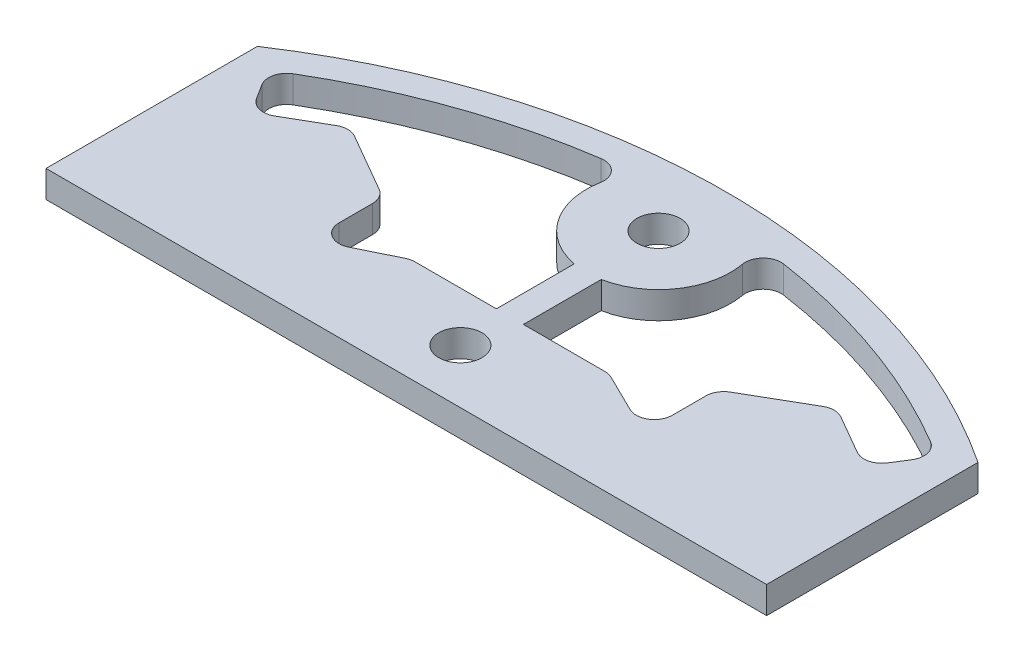
SolidWorks part; units mm, degrees
material "Acrylic (Medium-high impact)"
ref_plane "Front Plane" through (0, 0, 0) normal (0, 0, 1) x (1, 0, 0)
ref_plane "Top Plane" through (0, 0, 0) normal (0, 1, 0) x (1, 0, 0)
ref_plane "Right Plane" through (0, 0, 0) normal (1, 0, 0) x (0, 0, -1)
sketch "Sketch1" plane through (0, 0, 0) normal (0, 1, 0) x (1, 0, 0)
  line L0 (0, -85) -> (-32.4891, -64.8129) construction
  line L1 (0, -85) -> (0, 0) construction
  arc A0 (36.5434, -62.6165) -> (-36.5434, -62.6165) centre (0, 0) ccw
  arc A1 (30.0898, -61.3851) -> (-30.0898, -61.3851) centre (0, -85) ccw
  arc A2 (-30.0898, -61.3851) -> (-36.5434, -62.6165) centre (-34.0231, -58.2982) cw
  arc A3 (36.5434, -62.6165) -> (30.0898, -61.3851) centre (34.0231, -58.2982) cw
  dimension "D1" = 145
  dimension "D2" = 76.5
  dimension "D4" = 5
  dimension "D3" = 85
extrude "Boss-Extrude1" add sketch "Sketch1" along normal blind 3
sketch "Sketch10" plane through (0, 0, 0) normal (0, -1, 0) x (1, 0, 0)
  line L21 (-18.5, -44.8246) -> (-18.5, -52.9075)
  line L22 (-18.5, -52.9075) -> (-27, -57.815)
  line L23 (-27, -57.815) -> (-34, -53.7735)
  line L24 (-18.5, -48.0319) -> (-18.5, -51.7528)
  line L25 (-19.5, -53.4848) -> (-26, -57.2376)
  line L26 (-28, -57.2376) -> (-32.3362, -54.7341)
  line L31 (15.6199, -46.236) -> (11.4164, -48.2959)
  line L32 (11, -48.5) -> (-11, -48.5)
  line L33 (34, -53.7735) -> (27, -57.815)
  line L34 (27, -57.815) -> (18.5, -52.9075)
  line L35 (18.5, -52.9075) -> (18.5, -44.8246)
  line L36 (32.3362, -54.7341) -> (28, -57.2376)
  line L37 (26, -57.2376) -> (19.5, -53.4848)
  line L38 (18.5, -51.7528) -> (18.5, -48.0319)
  line L39 (10.5363, -48.5) -> (-10.5363, -48.5)
  line L40 (35.0267, -55.3973) -> (36.0573, -57.0273)
  line L41 (-11.4164, -48.2959) -> (-15.6199, -46.236)
  line L42 (-35.0267, -55.3973) -> (-36.0573, -57.0273)
  arc A21 (-35.0312, 60.0255) -> (35.0312, 60.0255) centre (0, 0) ccw
  arc A22 (-35.3852, -59.8175) -> (-10.1321, -68.7575) centre (0, 0) ccw
  arc A23 (10.1321, -68.7575) -> (35.3852, -59.8175) centre (0, 0) ccw
  circle A24 centre (0, -65) radius 8
  arc A25 (7.8724, -66.4231) -> (-7.8724, -66.4231) centre (0, -65) ccw
  arc A26 (-7.8724, -66.4231) -> (-10.1321, -68.7575) centre (-9.8405, -66.7788) cw
  arc A27 (7.8724, -66.4231) -> (10.1321, -68.7575) centre (9.8405, -66.7788) ccw
  arc A28 (36.0573, -57.0273) -> (35.3852, -59.8175) centre (34.3669, -58.0962) cw
  arc A29 (32.3362, -54.7341) -> (35.0267, -55.3973) centre (33.3362, -56.4661) cw
  arc A30 (28, -57.2376) -> (26, -57.2376) centre (27, -55.5056) cw
  arc A31 (19.5, -53.4848) -> (18.5, -51.7528) centre (20.5, -51.7528) cw
  arc A32 (18.5, -48.0319) -> (15.6199, -46.236) centre (16.5, -48.0319) ccw
  arc A33 (10.5363, -48.5) -> (11.4164, -48.2959) centre (10.5363, -46.5) ccw
  arc A34 (-10.5363, -48.5) -> (-11.4164, -48.2959) centre (-10.5363, -46.5) cw
  arc A35 (-18.5, -48.0319) -> (-15.6199, -46.236) centre (-16.5, -48.0319) cw
  arc A36 (-18.5, -51.7528) -> (-19.5, -53.4848) centre (-20.5, -51.7528) cw
  arc A37 (-26, -57.2376) -> (-28, -57.2376) centre (-27, -55.5056) cw
  arc A38 (-32.3362, -54.7341) -> (-35.0267, -55.3973) centre (-33.3362, -56.4661) ccw
  arc A39 (-36.0573, -57.0273) -> (-35.3852, -59.8175) centre (-34.3669, -58.0962) ccw
  point P23 (6.8312, -69.1635)
  dimension "D6" = 2
  dimension "D1" = 3
  dimension "D2" = 3
  dimension "D3" = 3
  dimension "D4" = 3
  dimension "D5" = 3
extrude "Cut-Extrude12" cut sketch "Sketch10" against normal through all contours L42 A39 A22 A26 A25 A27 A23 A28 L40 A29 L36 A30 L37 A31 L38 A32 L31 A33 L39 A34 L41 A35 L24 A36 L25 A37 L26 A38 region at (-17.155, 0, -46.9815) region at (-18.7098, 0, -52.7863) region at (-27, 0, -57.5727) region at (18.7098, 0, -52.7863) region at (27, 0, -57.5727)
sketch "Sketch11" plane through (0, 0, 0) normal (0, -1, 0) x (1, 0, 0)
  line L1 (40, -37) -> (-40, -37)
  line L2 (40, -37) -> (40, -77)
  line L3 (40, -77) -> (-40, -77)
  line L4 (-40, -37) -> (-40, -77)
  line L5 (40, -37) -> (-40, -77) construction
  line L6 (40, -77) -> (-40, -37) construction
  arc A0 (7.8724, -66.4231) -> (-7.8724, -66.4231) centre (0, -65) ccw construction
  point P0 (0, -57)
  dimension "D1" = 80
  dimension "D2" = 40
extrude "Cut-Extrude13" cut sketch "Sketch11" against normal through all flip side to cut
sketch "Sketch12" plane through (0, 0, 0) normal (0, -1, 0) x (1, 0, 0)
  circle A0 centre (0, -65) radius 2.4
  circle A1 centre (0, -43) radius 2.4
  dimension "D1" = 4.8
  dimension "D2" = 22
extrude "Cut-Extrude15" cut sketch "Sketch12" against normal through all
sketch "Sketch13" plane through (0, 0, 0) normal (0, -1, 0) x (1, 0, 0)
  line L0 (0, -65) -> (0, -53.7181) construction
  line L1 (1.5, -47.0524) -> (-1.5, -47.0524)
  line L2 (1.5, -47.0524) -> (1.5, -60.3839)
  line L3 (1.5, -60.3839) -> (-1.5, -60.3839)
  line L4 (-1.5, -47.0524) -> (-1.5, -60.3839)
  line L5 (1.5, -47.0524) -> (-1.5, -60.3839) construction
  line L6 (1.5, -60.3839) -> (-1.5, -47.0524) construction
  point P0 (0, -53.7181)
  dimension "D1" = 3
extrude "Boss-Extrude2" add sketch "Sketch13" against normal up to surface (3 mm away) up to face at (0, 3, -45.4)
equation "\"smallPulleyTeeth\"= 30"
equation "\"largePulleyTeeth\"= 30"
equation "\"eighthThick\"= 3.0mm"
equation "\"sixteenthThick\" = 1.7mm"
equation "\"quarterThick\"=6.0mm"
equation "\"OD\" = 145mm"
equation "\"puckAngle\" = 60.5deg"
equation "\"D1@Sketch1\"=\"OD\""
equation "\"puckDiam\" = 76.5mm"
equation "\"D2@Sketch1\"=\"puckDiam\""
equation "\"D1@Boss-Extrude1\"=\"eighthThick\""
equation "\"axlePress\" = 5.9mm"
equation "\"press\" = 0.2mm"
equation "\"wheelClear\" = 0.3mm"
equation "\"10-32clear\" = 4.8mm"
equation "\"6-32clear\" = 3.3mm"
equation "\"8-32clear\" = 4.0mm"
equation "\"wheelHeight\" = 22mm"
equation "\"wheelWell\" = 65mm"
equation "\"D1@Sketch3\"=\"wheelWell\""
equation "\"puckDist\" = 85mm"
equation "\"scoopFillet\" = 5mm"
equation "\"4-40clear\" = 3.0mm"
equation "\"D3@Sketch1\"=\"puckDist\""
equation "\"D4@Sketch1\"=\"scoopFillet\""
equation "\"D3@Sketch9\"=\"6-32clear\""
equation "\"D1@Sketch12\"=\"10-32clear\""
